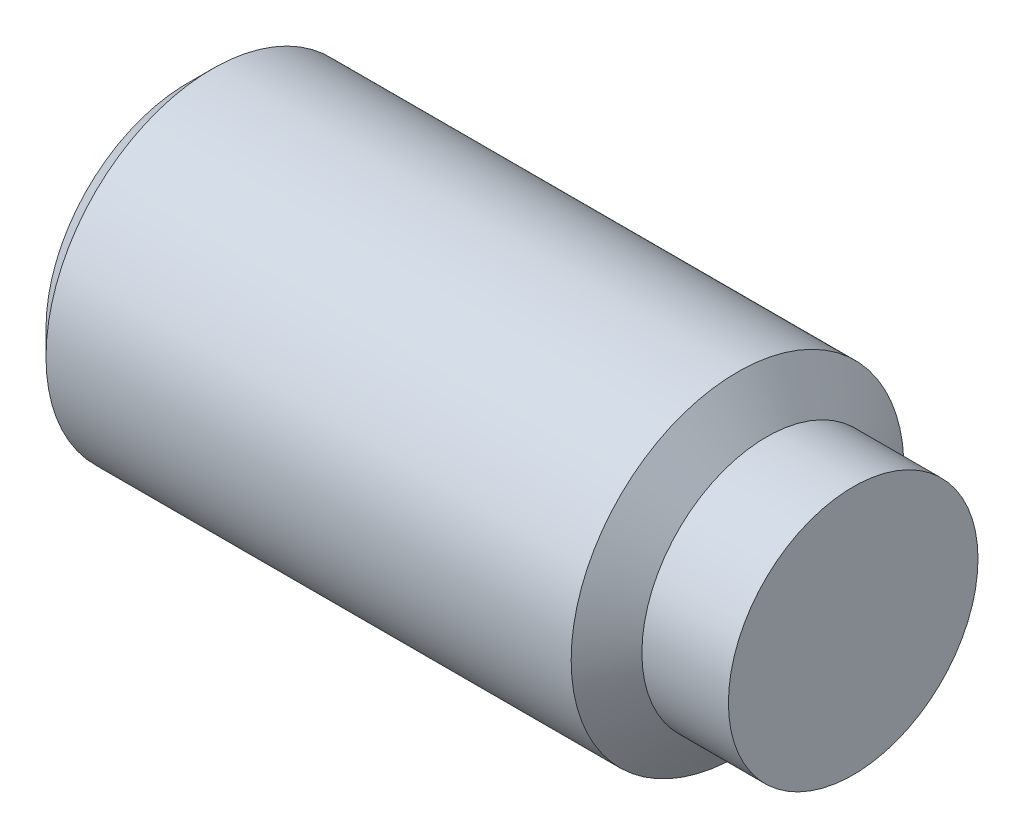
SolidWorks part; units mm, degrees
revolve "BaseBody" add sketch "BodySke" angle 360 about L5 other way angle 60
sketch "BodySke" plane through (0, 0, 0) normal (0, 0, 1) x (1, 0, 0)
  line L0 (0, 0) -> (0, 10.8102)
  line L1 (0, 10.8102) -> (1.8898, 12.7)
  line L2 (1.8898, 12.7) -> (41.9728, 12.7)
  line L3 (41.9728, 12.7) -> (44.196, 9.525)
  line L4 (50.8, 0) -> (0, 0)
  line L5 (-12.7, 0) -> (88.9, 0) construction
  line L6 (44.196, 9.525) -> (50.8, 9.525)
  line L7 (50.8, 9.525) -> (50.8, 0)
  line L8 (0, -10.8102) -> (1.8898, -12.7) construction
  line L9 (44.196, -9.525) -> (50.8, -9.525) construction
  line L10 (2.1082, 15.875) -> (2.1082, -3.175) construction
  dimension "Length" = 50.8
  dimension "D1" = 55
  dimension "Diameter" = 25.4
cosmetic thread "ThreadCosmetic" [suppressed] parameters "Thread_minor"=21.6205
ref_plane "Plane1" through (0, 0, 0) normal (0, 0, 1) x (1, 0, 0)
ref_plane "Plane2" through (0, 0, 0) normal (0, 1, 0) x (1, 0, 0)
ref_plane "Plane3" through (0, 0, 0) normal (1, 0, 0) x (0, 0, -1)
sketch "Sketch2" plane through (0, 0, 0) normal (-1, 0, 0) x (0, 0, 1)
  line L0 (4.1208, 7.1374) -> (-4.1208, 7.1374)
  line L1 (-4.1208, 7.1374) -> (-8.2416, 0)
  line L2 (4.1208, 7.1374) -> (8.2416, 0)
  line L3 (4.1208, -7.1374) -> (8.2416, 0)
  line L4 (4.1208, -7.1374) -> (-4.1208, -7.1374)
  line L5 (-4.1208, -7.1374) -> (-8.2416, 0)
  dimension "D2" = 7.1374
  dimension "D3" = 7.1374
extrude "Hex" cut sketch "Sketch2" against normal blind 14.2748
sketch "Sketch4" plane through (0, 4.7709, -0.5249) normal (-1, 0, 0) x (0, 0, 1)
  line L0 (0.5249, -4.7709) -> (10.6976, -4.7709)
  line L1 (0.5249, -4.7709) -> (6.6732, -1.2211) construction
  line L2 (0.5249, -4.7709) -> (5.6112, 4.0389)
  line L3 (8.9666, -2.6687) -> (10.2861, -1.9069)
  line L4 (6.5663, 1.4888) -> (7.8858, 2.2506)
  arc A0 (8.9666, -2.6687) -> (6.5663, 1.4888) centre (0.5249, -4.7709) ccw
  arc A1 (10.6976, -4.7709) -> (10.2861, -1.9069) centre (0.5249, -4.7709) ccw
  arc A2 (5.6112, 4.0389) -> (7.8858, 2.2506) centre (0.5249, -4.7709) cw
  circle A3 centre (0.5249, -4.7709) radius 8.6995 construction
  circle A4 centre (0.5249, -4.7709) radius 10.1727 construction
  dimension "Spline_n_dim" = 17.399
  dimension "Spline_m_dim" = 20.3454
  dimension "D1" = 30
  dimension "Spline_p_dim" = 4.8006
  dimension "D3" = 2.4003
extrude "Spline" [suppressed] cut sketch "Sketch4" against normal blind 12.7
pattern_circular "CirPattern1" [suppressed] count 6 every 60 about axis through (-12.7, 0, 0) along (1, 0, 0)
sketch "ThdSchSke" plane through (0, 0, 0) normal (0, 0, 1) x (1, 0, 0)
  line L0 (1.8898, -10.8102) -> (0.5665, -12.7)
  line L1 (1.8898, -10.8102) -> (3.213, -12.7)
  line L2 (3.213, -12.7) -> (3.213, -15.875)
  line L3 (-3.175, 0) -> (5.1513, 0) construction
  line L4 (1.8898, 12.7) -> (1.8898, -12.7) construction
  line L5 (3.213, -15.875) -> (0.5665, -15.875)
  line L6 (0.5665, -15.875) -> (0.5665, -12.7)
  dimension "Thread_minor" = 21.6205
  dimension "Diameter" = 25.4
revolve "ThreadSchematic" [suppressed] cut sketch "ThdSchSke" angle 360 about L3
pattern_linear "ThdSchPat" [suppressed]
equation "\"D2@Sketch2\" = \"Hex_size@Sketch2\" / 2"
equation "\"D3@Sketch2\" = \"Hex_size@Sketch2\" / 2"
equation "\"Thread_minor@ThreadCosmetic\" = \"Minor_dia@BodySke\""
equation "\"D1@Sketch4\" = \"Spline_a_dim@Sketch4\" / 2"
equation "\"D3@Sketch4\" = \"Spline_p_dim@Sketch4\" / 2"
equation "\"D2@CirPattern1\" = \"Spline_a_dim@Sketch4\""
equation "\"Num_teeth@CirPattern1\" = 360 / \"D2@CirPattern1\""
equation "\"Thread_minor@ThdSchSke\" = \"Thread_minor@ThreadCosmetic\""
equation "\"Diameter@ThdSchSke\" = \"Diameter@BodySke\""
equation "\"Overcut@ThdSchSke\" = \"Diameter@BodySke\" * 1.25"
equation "\"Num_threads@ThdSchPat\" = int( (\"Length@BodySke\" - ( ( ( \"Diameter@BodySke\" - \"Minor_dia@BodySke\" ) * 0.5 ) / tan( \"Drive_ch_ang@BodySke\" * 0.017453292 ) ) - \"Dog_len@BodySke\" ) / \"Advance@BodySke\" + 0.999 )  + 1"
equation "\"Advance@ThdSchPat\" = (\"Length@BodySke\" - ( ( ( \"Diameter@BodySke\" - \"Minor_dia@BodySke\" ) * 0.5 ) / tan( \"Drive_ch_ang@BodySke\" * 0.017453292 ) ) - \"Dog_len@BodySke\" ) /  (\"Num_threads@ThdSchPat\" - 1) 'relax it"
equation "\"Num_threads@ThdSchPat\" = \"Num_threads@ThdSchPat\" - sgn( \"Num_threads@ThdSchPat\" - 1) '---chamfered tips only---"
